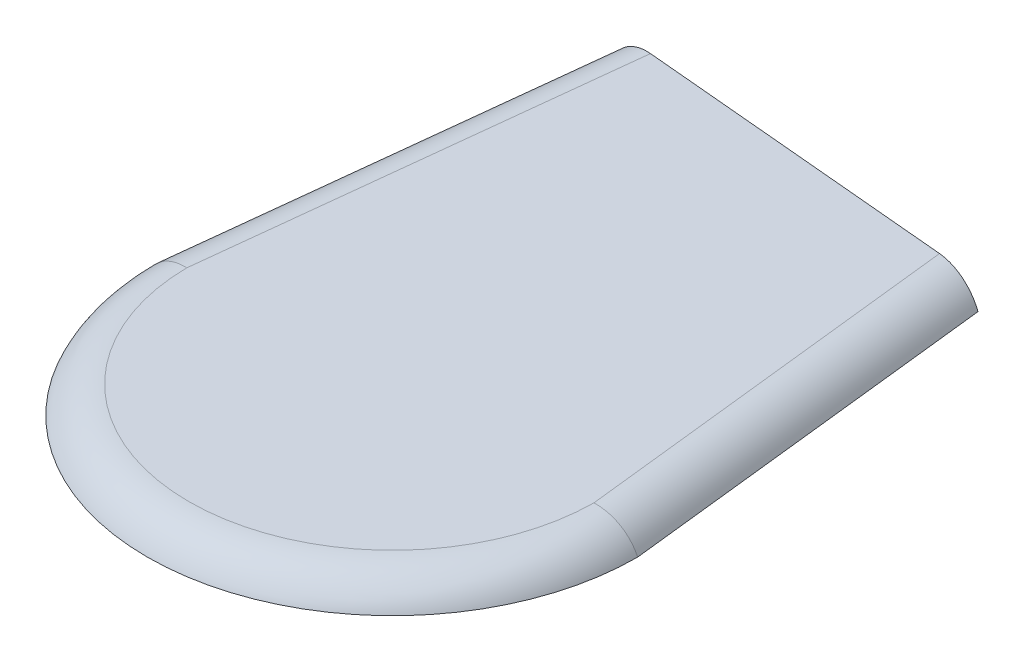
SolidWorks part; units mm, degrees
ref_plane "Front Plane" through (0, 0, 0) normal (0, 0, 1) x (1, 0, 0)
ref_plane "Top Plane" through (0, 0, 0) normal (0, 1, 0) x (1, 0, 0)
ref_plane "Right Plane" through (0, 0, 0) normal (1, 0, 0) x (0, 0, -1)
sketch "Sketch1" plane through (0, 0, 0) normal (0, 1, 0) x (1, 0, 0)
  line L0 (-68.7161, 28.1705) -> (-69.4925, 21.1705)
  line L1 (-21.7208, 49.3214) -> (-65.9278, 53.3078)
  line L2 (-65.9278, 53.3078) -> (-68.7161, 28.1705)
  line L3 (-68.7161, 28.1705) -> (-32.0454, 28.1705)
  line L4 (-32.0454, 28.1705) -> (-32.0454, -2.0922)
  line L5 (-32.0454, -2.0922) -> (-56.0454, -2.0922)
  line L6 (-56.0454, -2.0922) -> (-56.0454, 21.1705)
  line L7 (-56.0454, 21.1705) -> (-69.4925, 21.1705)
  line L8 (-69.4925, 21.1705) -> (-71.0454, 7.1705)
  line L9 (-17.0454, 7.1705) -> (-21.7208, 49.3214)
  arc A0 (-71.0454, 7.1705) -> (-17.0454, 7.1705) centre (-44.0454, 7.1705) ccw
extrude "Boss-Extrude1" add sketch "Sketch1" along normal blind 3 contours L8 A0 L9 L1 L2 L3 L4 L5 L6 L7 | L7 L6 L5 L4 L3 L0 region at (-46.117, 0, -14.3355) region at (-66.4184, 0, -40.6389)
fillet "Fillet1" radius 5 3 edges at (-19.3831, 3, -28.2459) (-68.4866, 3, -30.2391) (-44.0454, 3, 19.8295)
